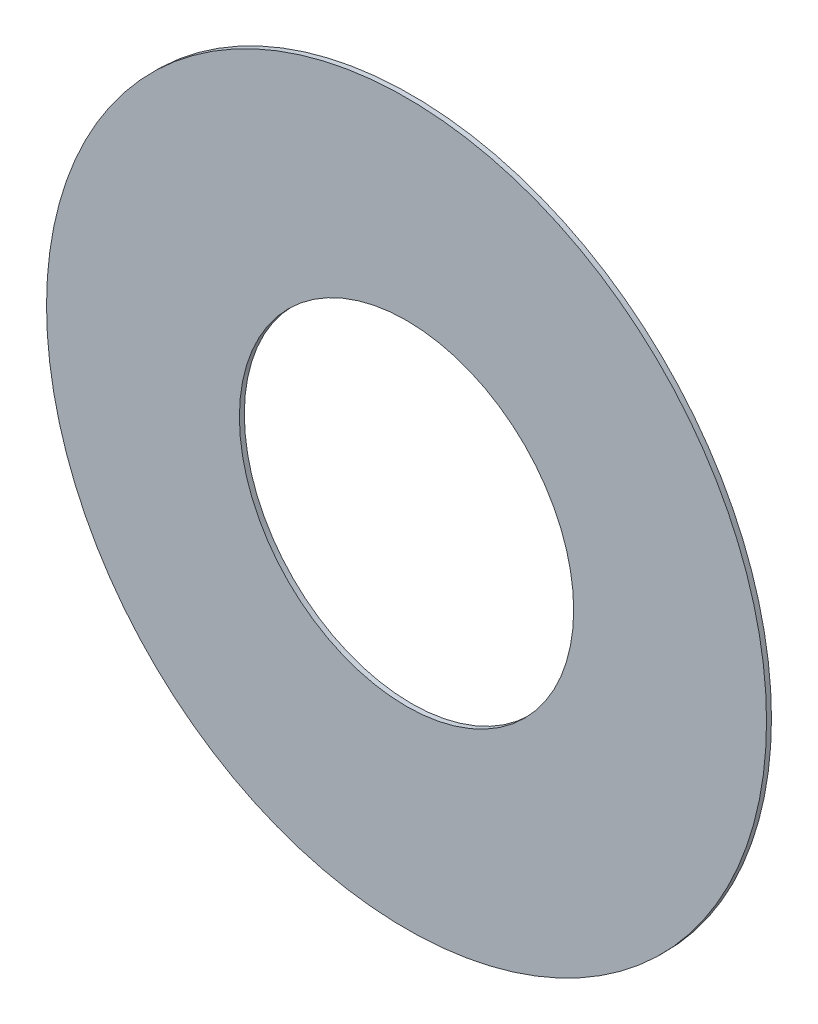
SolidWorks part; units mm, degrees
ref_plane "Front Plane" through (0, 0, 0) normal (0, 0, 1) x (1, 0, 0)
ref_plane "Top Plane" through (0, 0, 0) normal (0, 1, 0) x (1, 0, 0)
ref_plane "Right Plane" through (0, 0, 0) normal (1, 0, 0) x (0, 0, -1)
ref_plane "Plane1" through (0, 0, 0) normal (0, 0, -1) x (-1, 0, 0)
sketch "Sketch1" plane through (0, 0, 0) normal (0, 0, -1) x (-1, 0, 0)
  circle A0 centre (0, 0) radius 5.5563
  circle A1 centre (0, 0) radius 2.5797
extrude "Boss-Extrude1" add sketch "Sketch1" against normal blind 0.0762
ref_axis "Axis1" through (0, 0, 1.1899) along (0, 0, -1)
